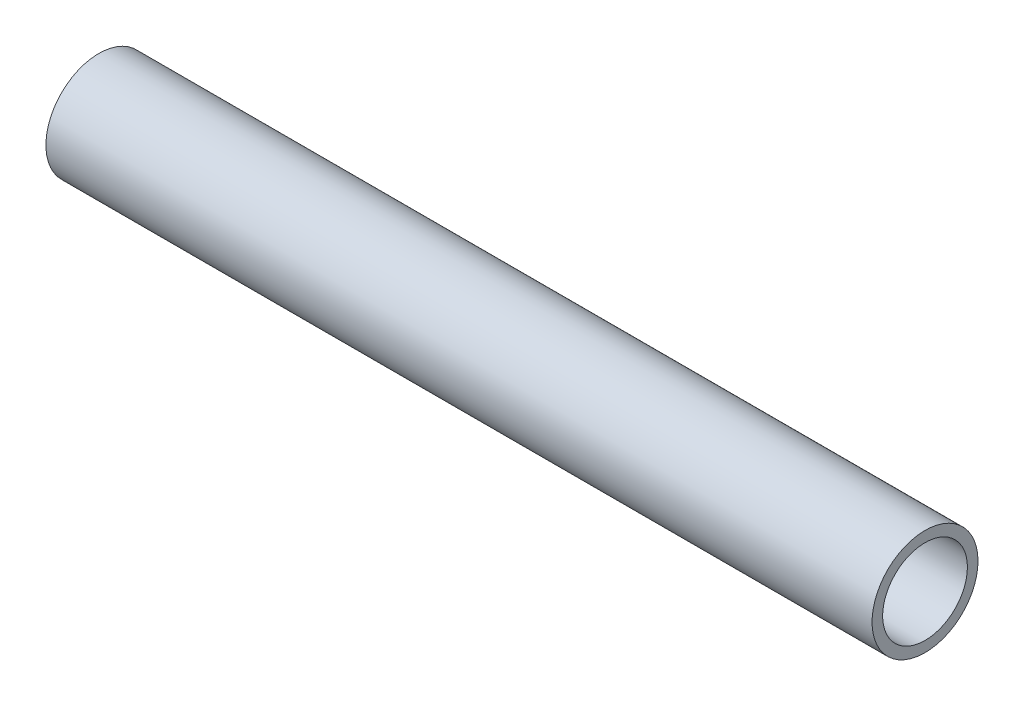
SolidWorks part; units mm, degrees
material "PC High Viscosity"
ref_plane "Front Plane" through (0, 0, 0) normal (0, 0, 1) x (1, 0, 0)
ref_plane "Top Plane" through (0, 0, 0) normal (0, 1, 0) x (1, 0, 0)
ref_plane "Right Plane" through (0, 0, 0) normal (1, 0, 0) x (0, 0, -1)
sketch "Sketch1" plane through (0, 0, 0) normal (1, 0, 0) x (0, 0, -1)
  circle A0 centre (0, 0) radius 15.875
  dimension "D1" = 31.75
extrude "Extrude-Thin1" add sketch "Sketch1" along normal mid plane 247.6182 thin thin type one direction reverse wall 3.175
